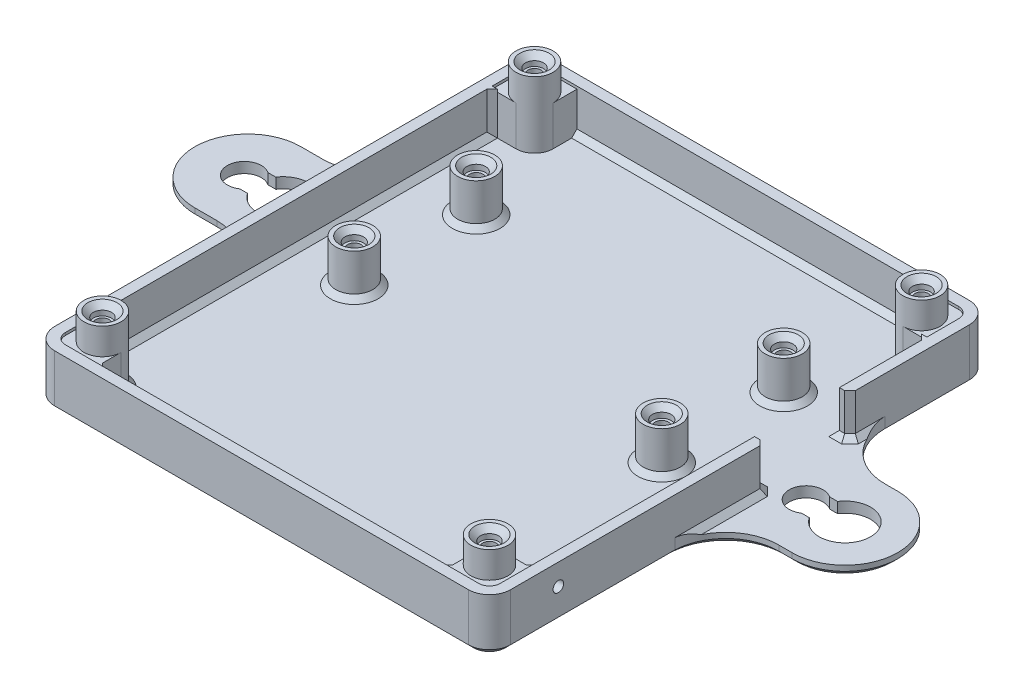
SolidWorks part; units mm, degrees
note: The reader was unsure of these and kept them because the rebuilt part matched: shared geometry of "Sketch2<3>".
ref_plane "Front Plane" through (0, 0, 0) normal (0, 0, 1) x (1, 0, 0)
ref_plane "Top Plane" through (0, 0, 0) normal (0, 1, 0) x (1, 0, 0)
ref_plane "Right Plane" through (0, 0, 0) normal (1, 0, 0) x (0, 0, -1)
sketch "Sketch1" plane through (0, 0, 0) normal (0, 1, 0) x (1, 0, 0)
  line L0 (-65.617, -16.3721) -> (-0.617, -16.3721)
  line L1 (-62.117, 10.1279) -> (-4.117, 10.1279)
  line L2 (-62.117, 10.1279) -> (-62.117, -12.8721)
  line L3 (-65.617, 13.6279) -> (-0.617, 13.6279)
  line L4 (-65.617, 13.6279) -> (-65.617, -16.3721)
  line L5 (-62.117, -12.8721) -> (-4.117, -12.8721)
  line L6 (-0.617, 13.6279) -> (-0.617, -16.3721)
  line L7 (-4.117, 10.1279) -> (-4.117, -12.8721)
  line L8 (-24.217, 16.7282) -> (-24.217, 15.4455)
  line L9 (-11.617, 16.7282) -> (-11.617, 15.4455)
  dimension "D1" = 65
  dimension "D2" = 30
  dimension "D3" = 58
  dimension "D4" = 23
  dimension "D5" = 3.5
  dimension "D6" = 3.5
sketch "Sketch2" plane through (0, 0, 0) normal (0, 1, 0) x (1, 0, 0)
  line L1 (-0.617, 13.6279) -> (-0.617, -16.3721) construction
  line L2 (-65.617, 13.6279) -> (-65.617, -16.3721) construction
  line L3 (-65.617, 13.6279) -> (-0.617, 13.6279) construction
  line L4 (17.3223, -7.9561) -> (18.8027, -7.9561)
  line L5 (17.3223, -2.6407) -> (18.8027, -2.6407)
  line L6 (15.54, -5.2984) -> (22.8493, -5.2984)
  line L7 (-73.617, 30.6279) -> (-73.617, -55.8721)
  line L8 (-65.617, -16.3721) -> (-0.617, -16.3721) construction
  line L9 (-91.5099, -5.2984) -> (-84.2007, -5.2984)
  line L10 (-71.617, -57.8721) -> (6.383, -57.8721)
  line L11 (-75.617, 30.6279) -> (-75.617, 14.7016)
  line L12 (-88.6355, -7.9561) -> (-87.1552, -7.9561)
  line L13 (-88.6355, -2.6407) -> (-87.1552, -2.6407)
  line L14 (8.383, 30.6279) -> (8.383, -55.8721)
  line L15 (-71.617, 32.6279) -> (6.383, 32.6279)
  line L16 (-71.617, -59.8721) -> (6.383, -59.8721)
  line L17 (10.383, 30.6279) -> (10.383, 14.7016)
  line L18 (-71.617, 34.6279) -> (6.383, 34.6279)
  line L19 (-85.617, 4.7016) -> (-89.754, 4.7016)
  line L20 (-85.617, -15.2984) -> (-89.754, -15.2984)
  line L21 (22.8493, 4.7016) -> (20.383, 4.7016)
  line L22 (22.8493, -15.2984) -> (20.383, -15.2984)
  line L23 (10.383, -24.9016) -> (10.383, -55.8721)
  line L24 (10.383, 30.6279) -> (10.383, -55.8721) construction
  line L25 (-75.617, -25.2984) -> (-75.617, -55.8721)
  line L26 (-75.617, 30.6279) -> (-75.617, -55.8721) construction
  arc A0 (-71.617, -57.8721) -> (-73.617, -55.8721) centre (-71.617, -55.8721) cw
  arc A1 (6.383, -57.8721) -> (8.383, -55.8721) centre (6.383, -55.8721) ccw
  arc A2 (8.383, 30.6279) -> (6.383, 32.6279) centre (6.383, 30.6279) ccw
  arc A3 (-71.617, 32.6279) -> (-73.617, 30.6279) centre (-71.617, 30.6279) ccw
  arc A4 (-71.617, -59.8721) -> (-75.617, -55.8721) centre (-71.617, -55.8721) cw
  arc A5 (6.383, -59.8721) -> (10.383, -55.8721) centre (6.383, -55.8721) ccw
  arc A6 (10.383, 30.6279) -> (6.383, 34.6279) centre (6.383, 30.6279) ccw
  arc A7 (-71.617, 34.6279) -> (-75.617, 30.6279) centre (-71.617, 30.6279) ccw
  arc A8 (18.8027, -7.9561) -> (18.8027, -2.6407) centre (22.8493, -5.2984) ccw
  arc A9 (17.3223, -2.6407) -> (17.3223, -7.9561) centre (15.54, -5.2984) ccw
  arc A10 (-88.6355, -2.6407) -> (-88.6355, -7.9561) centre (-90.4179, -5.2984) ccw
  arc A11 (-87.1552, -7.9561) -> (-87.1552, -2.6407) centre (-83.1086, -5.2984) ccw
  arc A12 (-89.754, 4.7016) -> (-89.754, -15.2984) centre (-89.754, -5.2984) ccw
  arc A13 (22.8493, 4.7016) -> (22.8493, -15.2984) centre (22.8493, -5.2984) cw
  arc A14 (-75.617, -25.2984) -> (-85.617, -15.2984) centre (-85.617, -25.2984) ccw
  arc A15 (-85.617, 4.7016) -> (-75.617, 14.7016) centre (-85.617, 14.7016) ccw
  arc A16 (10.383, 14.7016) -> (20.383, 4.7016) centre (20.383, 14.7016) ccw
  arc A17 (20.383, -15.2984) -> (10.383, -24.9016) centre (20.383, -25.3066) ccw
  dimension "D4" = 2
  dimension "D3" = 19
  dimension "D1" = 41.5
  dimension "D2" = 9
  dimension "D6" = 8
  dimension "D5" = 2
extrude "Boss-Extrude1" add sketch "Sketch2" along normal blind 10 contours A17 L22 A13 L21 A16 L17 A6 L18 A7 L11 A15 L19 A12 L20 A14 L25 A4 L16 A5 L23 A11 L12 A10 L13 A9 L5 A8 L4 A3 L15 A2 L14 A1 L10 A0 L7
extrude "Boss-Extrude2" add sketch "Sketch2<3>" along normal blind 2 contours L15 A3 L7 A0 L10 A1 L14 A2 | L15 A3 L7 A0 L10 A1 L14 A2
sketch "Sketch2<3>" plane through (0, 0, 0) normal (0, 1, 0) x (1, 0, 0) same geometry as "Sketch2"
sketch "Sketch24" plane through (0, 10, 0) normal (0, 1, 0) x (1, 0, 0)
  line L1 (10.383, -24.9016) -> (33.3603, -24.9016)
  line L2 (10.383, -24.9016) -> (10.383, 14.7016)
  line L3 (10.383, 14.7016) -> (33.3603, 14.7016)
  line L4 (33.3603, -24.9016) -> (33.3603, 14.7016)
  line L5 (-75.617, -25.2984) -> (-102.575, -25.2984)
  line L6 (-75.617, -25.2984) -> (-75.617, 14.7016)
  line L7 (-75.617, 14.7016) -> (-102.575, 14.7016)
  line L8 (-102.575, -25.2984) -> (-102.575, 14.7016)
extrude "Cut-Extrude6" cut sketch "Sketch24" against normal offset from surface (8 mm away) 2 up to face at (-32.7771, 0, 8.211)
sketch "Sketch4" plane through (0, 2, 0) normal (0, 1, 0) x (1, 0, 0)
  line L12 (-32.617, 32.6279) -> (-32.617, -57.8721) construction
  line L13 (-71.617, -57.8721) -> (6.383, -57.8721) construction
  circle A0 centre (-62.117, -12.8721) radius 3.5
  arc A1 (-58.617, 10.1279) -> (-65.617, 10.1279) centre (-62.117, 10.1279) cw
  arc A2 (-65.617, 10.1279) -> (-58.617, 10.1279) centre (-62.117, 10.1279) cw
  arc A3 (-7.617, 10.1279) -> (-0.617, 10.1279) centre (-4.117, 10.1279) cw
  arc A6 (-0.617, 10.1279) -> (-7.617, 10.1279) centre (-4.117, 10.1279) cw
  circle A7 centre (-4.117, -12.8721) radius 3.5
extrude "Boss-Extrude3" add sketch "Sketch4" along normal blind 8
sketch "Sketch9" plane through (0, 2, 0) normal (0, 1, 0) x (1, 0, 0)
  line L0 (0.383, -57.8721) -> (6.383, -57.8721)
  line L1 (8.383, -55.8721) -> (8.383, -49.8721)
  line L2 (-69.117, -49.8721) -> (-73.617, -49.8721)
  line L3 (-71.617, -57.8721) -> (-65.617, -57.8721)
  line L4 (-73.617, -49.8721) -> (-73.617, -55.8721)
  line L5 (8.383, -49.8721) -> (3.883, -49.8721)
  line L6 (-65.617, -57.8721) -> (-65.617, -53.3721)
  line L7 (0.383, -53.3721) -> (0.383, -57.8721)
  line L8 (6.383, 32.6279) -> (0.383, 32.6279)
  line L9 (3.883, 24.6279) -> (8.383, 24.6279)
  line L10 (8.383, 24.6279) -> (8.383, 30.6279)
  line L11 (0.383, 32.6279) -> (0.383, 28.1279)
  line L12 (-73.617, 24.6279) -> (-69.117, 24.6279)
  line L13 (-65.617, 28.1279) -> (-65.617, 32.6279)
  line L14 (-73.617, 30.6279) -> (-73.617, 24.6279)
  line L15 (-65.617, 32.6279) -> (-71.617, 32.6279)
  arc A0 (6.383, -57.8721) -> (8.383, -55.8721) centre (6.383, -55.8721) ccw
  arc A1 (-65.617, -53.3721) -> (-69.117, -49.8721) centre (-69.117, -53.3721) ccw
  arc A2 (-73.617, -55.8721) -> (-71.617, -57.8721) centre (-71.617, -55.8721) ccw
  arc A3 (3.883, -49.8721) -> (0.383, -53.3721) centre (3.883, -53.3721) ccw
  arc A4 (8.383, 30.6279) -> (6.383, 32.6279) centre (6.383, 30.6279) ccw
  arc A5 (0.383, 28.1279) -> (3.883, 24.6279) centre (3.883, 28.1279) ccw
  arc A6 (-69.117, 24.6279) -> (-65.617, 28.1279) centre (-69.117, 28.1279) ccw
  arc A7 (-71.617, 32.6279) -> (-73.617, 30.6279) centre (-71.617, 30.6279) ccw
  dimension "D1" = 2
  dimension "D2" = 2
  dimension "D3" = 2
  dimension "D4" = 2
extrude "Boss-Extrude4" add sketch "Sketch9" along normal offset from surface (12.5 mm away) 4.5 up to face at (-32.617, 10, 12.6221) offset beyond the face yes
chamfer "Chamfer3" distance 1 angle 45 20 edges at (-75.617, 0, -22.6647) (-75.617, 0, 40.5853) (-74.4454, 0, 58.7006) (-32.617, 0, 59.8721) (9.2114, 0, 58.7006) (10.383, 0, 40.3869) (-78.5459, 0, 18.2274) (-87.6855, 0, 15.2984) (13.4508, 0, 18.088) (-99.754, 0, 5.2984) (21.6161, 0, 15.2984) (-87.6855, 0, -4.7016) (32.8493, 0, 5.2984) (-78.5459, 0, -7.6305) (21.6161, 0, -4.7016) (13.312, 0, -7.6305) (-74.4454, 0, -33.4563) (10.383, 0, -22.6647) (9.2114, 0, -33.4563) (-32.617, 0, -34.6279)
chamfer "Chamfer5" distance 1 angle 45 13 edges at (-4.117, 2, 9.3721) (8.383, 2, 12.6221) (-4.117, 2, -13.6279) (-32.617, 2, -32.6279) (-73.617, 2, 12.6221) (-32.617, 2, 57.8721) (-62.117, 2, -13.6279) (-62.117, 2, 9.3721) (-65.617, 2, 55.6221) (-66.6421, 2, 50.8973) (-71.367, 2, 49.8721) (8.383, 6, -24.6279) (-73.617, 6, -24.6279)
hole_wizard "Ø2.5 (2.5) Diameter Hole1" positions "Sketch14" profile "Sketch13" hole size "Ø2.5" standard "ANSI Metric"
sketch "Sketch14" plane through (0, 10, 0) normal (0, 1, 0) x (1, 0, 0)
  point P0 (-62.117, 10.1279)
  point P4 (-4.117, 10.1279)
  point P8 (-62.117, -12.8721)
  point P12 (-4.117, -12.8721)
sketch "Sketch13" plane through (-62.117, 10, -10.1279) normal (1, 0, 0) x (0, 0, 1)
  line L0 (0, 0) -> (0, 8)
  line L1 (0, 8) -> (1.25, 8)
  line L2 (1.25, 8) -> (1.25, 1.5)
  line L3 (1.25, 1.5) -> (2.75, 0)
  line L5 (2.75, 0) -> (0, 0)
  line L6 (-1.25, 1.5) -> (-2.75, 0) construction
  line L10 (0, 8) -> (-1.25, 8) construction
  line L11 (0, -6.35) -> (0, 107.95) construction
  dimension "Hole Dia." = 2.5
  dimension "Hole Depth" = 8
  dimension "Near C'Sink Dia." = 5.5
  dimension "Near C'Sink Angle" = 90
  dimension "Drill Angle" = 180
hole_wizard "Ø3.5 (3.5) Diameter Hole1" positions "Sketch16" profile "Sketch15" hole size "Ø3.5" standard "ANSI Metric"
sketch "Sketch16" plane through (0, 10, 0) normal (0, 1, 0) x (1, 0, 0)
  point P0 (-62.117, 10.1279)
  point P4 (-4.117, 10.1279)
  point P8 (-62.117, -12.8721)
  point P12 (-4.117, -12.8721)
sketch "Sketch15" plane through (-62.117, 10, -10.1279) normal (1, 0, 0) x (0, 0, 1)
  line L0 (0, 0) -> (0, 2)
  line L1 (0, 2) -> (1.75, 2)
  line L2 (1.75, 2) -> (1.75, 0)
  line L5 (1.75, 0) -> (0, 0)
  line L10 (0, 2) -> (-1.75, 2) construction
  line L11 (0, -6.35) -> (0, 107.95) construction
  dimension "Hole Dia." = 3.5
  dimension "Hole Depth" = 2
  dimension "Drill Angle" = 180
hole_wizard "Ø2.5 (2.5) Diameter Hole2" positions "Sketch18" profile "Sketch17" hole size "Ø2.5" standard "ANSI Metric"
sketch "Sketch18" plane through (0, 14.5, 0) normal (0, 1, 0) x (1, 0, 0)
  point P0 (-69.117, -53.3721)
  point P7 (3.883, -53.3721)
  point P14 (-69.117, 28.1279)
  point P17 (3.883, 28.1279)
sketch "Sketch17" plane through (-69.117, 14.5, 53.3721) normal (1, 0, 0) x (0, 0, 1)
  line L0 (0, 0) -> (0, 12.5)
  line L1 (0, 12.5) -> (1.25, 12.5)
  line L2 (1.25, 12.5) -> (1.25, 1.5)
  line L3 (1.25, 1.5) -> (2.75, 0)
  line L5 (2.75, 0) -> (0, 0)
  line L6 (-1.25, 1.5) -> (-2.75, 0) construction
  line L10 (0, 12.5) -> (-1.25, 12.5) construction
  line L11 (0, -6.35) -> (0, 107.95) construction
  dimension "Hole Dia." = 2.5
  dimension "Hole Depth" = 12.5
  dimension "Near C'Sink Dia." = 5.5
  dimension "Near C'Sink Angle" = 90
  dimension "Drill Angle" = 180
hole_wizard "Ø3.4 (3.4) Diameter Hole1" positions "Sketch20" profile "Sketch19" hole size "Ø3.4" standard "ANSI Metric"
sketch "Sketch20" plane through (0, 14.5, 0) normal (0, 1, 0) x (1, 0, 0)
  point P0 (-69.117, -53.3721)
  point P7 (3.883, -53.3721)
  point P10 (-69.117, 28.1279)
  point P13 (3.883, 28.1279)
sketch "Sketch19" plane through (-69.117, 14.5, 53.3721) normal (1, 0, 0) x (0, 0, 1)
  line L0 (0, 0) -> (0, 2)
  line L1 (0, 2) -> (1.7, 2)
  line L2 (1.7, 2) -> (1.7, 0)
  line L5 (1.7, 0) -> (0, 0)
  line L10 (0, 2) -> (-1.7, 2) construction
  line L11 (0, -6.35) -> (0, 107.95) construction
  dimension "Hole Dia." = 3.4
  dimension "Hole Depth" = 2
  dimension "Drill Angle" = 180
sketch "Sketch21" plane through (10.383, 0, 0) normal (1, 0, 0) x (0, 0, -1)
  line L0 (-55.8721, 10) -> (30.6279, 10) construction
  line L1 (-7.8721, 10) -> (8.1279, 10)
  line L2 (-7.8721, 10) -> (-7.8721, 2)
  line L3 (-7.8721, 2) -> (8.1279, 2)
  line L4 (8.1279, 10) -> (8.1279, 2)
  line L5 (0.1279, 10) -> (0.1279, 2) construction
  dimension "D1" = 8
  dimension "D2" = 16
  dimension "D3" = 10
extrude "Cut-Extrude3" cut sketch "Sketch21" against normal up to next
chamfer "Chamfer9" distance 1 angle 45 2 edges at (10.383, 6, 7.8721) (10.383, 6, -8.1279)
sketch "Sketch22" plane through (0, 14.5, 0) normal (0, 1, 0) x (1, 0, 0)
  line L1 (3.883, -49.8721) -> (8.383, -49.8721)
  line L2 (0.383, -53.3721) -> (0.383, -57.8721)
  line L3 (0.383, -57.8721) -> (6.383, -57.8721)
  line L4 (-65.617, -53.3721) -> (-65.617, -57.8721)
  line L5 (-65.617, -57.8721) -> (-65.617, -53.3721) construction
  line L6 (-65.617, -57.8721) -> (-71.617, -57.8721)
  line L7 (-69.117, -49.8721) -> (-73.617, -49.8721)
  line L8 (-73.617, -49.8721) -> (-73.617, -55.8721)
  line L9 (-65.617, -57.8721) -> (-65.617, -53.3721) construction
  line L10 (8.383, -49.8721) -> (8.383, -55.8721)
  line L11 (0.383, 32.6279) -> (6.383, 32.6279)
  line L12 (0.383, 28.1279) -> (0.383, 32.6279)
  line L13 (8.383, 24.6279) -> (8.383, 30.6279)
  line L14 (3.883, 24.6279) -> (8.383, 24.6279)
  line L15 (-65.617, 28.1279) -> (-65.617, 32.6279)
  line L16 (-65.617, 32.6279) -> (-71.617, 32.6279)
  line L17 (-69.117, 24.6279) -> (-73.617, 24.6279)
  line L18 (-73.617, 24.6279) -> (-73.617, 30.6279)
  arc A0 (3.883, -49.8721) -> (1.8244, -56.2027) centre (3.883, -53.3721) cw
  arc A1 (-65.617, -53.3721) -> (-71.4428, -50.7567) centre (-69.117, -53.3721) cw
  arc A2 (-71.4428, -50.7567) -> (-69.117, -49.8721) centre (-69.117, -53.3721) cw
  arc A3 (-65.617, -53.3721) -> (-69.117, -49.8721) centre (-69.117, -53.3721) ccw construction
  arc A4 (-71.617, -57.8721) -> (-73.617, -55.8721) centre (-71.617, -55.8721) cw
  arc A5 (1.8244, -56.2027) -> (0.383, -53.3721) centre (3.883, -53.3721) cw
  arc A6 (8.383, -55.8721) -> (6.383, -57.8721) centre (6.383, -55.8721) cw
  arc A7 (6.383, 32.6279) -> (8.383, 30.6279) centre (6.383, 30.6279) cw
  arc A8 (6.7136, 26.0693) -> (3.883, 24.6279) centre (3.883, 28.1279) cw
  arc A9 (0.383, 28.1279) -> (6.7136, 26.0693) centre (3.883, 28.1279) cw
  arc A10 (-67.0584, 30.9584) -> (-65.617, 28.1279) centre (-69.117, 28.1279) cw
  arc A11 (-73.617, 30.6279) -> (-71.617, 32.6279) centre (-71.617, 30.6279) cw
  arc A12 (-69.117, 24.6279) -> (-67.0584, 30.9584) centre (-69.117, 28.1279) cw
  dimension "D1" = 2
  dimension "D2" = 2
  dimension "D3" = 2
  dimension "D4" = 2
extrude "Cut-Extrude4" cut sketch "Sketch22" against normal blind 5
chamfer "Chamfer4" distance 1 angle 45 4 edges at (-65.617, 6.25, 57.8721) (-73.617, 6.25, 49.8721) (8.383, 6.25, 49.8721) (0.383, 6.25, 57.8721)
sketch "Sketch23" plane through (-75.617, 0, 0) normal (-1, 0, 0) x (0, 0, 1)
  line L1 (59.8721, 10) -> (59.8721, 1) construction
  line L2 (-30.6279, 10) -> (55.8721, 10) construction
  circle A0 centre (46.8721, 6) radius 1
  dimension "D1" = 4
  dimension "D2" = 13
extrude "Cut-Extrude5" cut sketch "Sketch23" against normal through all and the other way through all
chamfer "Chamfer10" distance 1 angle 45 7 edges at (9.883, 2, -8.6279) (10.383, 2, -11.9147) (9.883, 2, 8.3721) (10.383, 2, 16.8869) (-75.617, 2, 5.2984) (8.383, 2, -8.1279) (8.383, 2, 7.8721)
